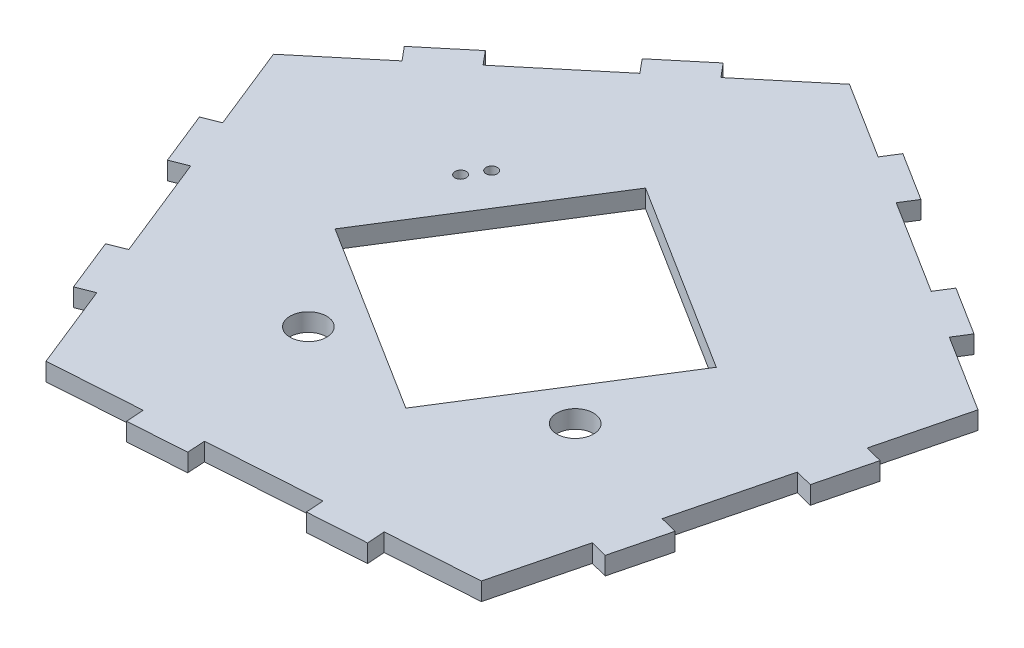
SolidWorks part; units mm, degrees
ref_plane "Front Plane" through (0, 0, 0) normal (0, 0, 1) x (1, 0, 0)
ref_plane "Top Plane" through (0, 0, 0) normal (0, 1, 0) x (1, 0, 0)
ref_plane "Right Plane" through (0, 0, 0) normal (1, 0, 0) x (0, 0, -1)
sketch "Sketch1" plane through (0, 0, 0) normal (0, 1, 0) x (1, 0, 0)
  line L1 (-59.9258, 15.1181) -> (-32.8962, -52.3211)
  line L2 (-32.8962, -52.3211) -> (39.5948, -47.4543)
  line L3 (39.5948, -47.4543) -> (57.3672, 22.9927)
  line L4 (57.3672, 22.9927) -> (-4.14, 61.6646)
  line L5 (-4.14, 61.6646) -> (-59.9258, 15.1181)
  circle A0 centre (0, 0) radius 50 construction
  dimension "D1" = 100
extrude "Boss-Extrude1" add sketch "Sketch1" along normal blind 3.18
ref_axis "Axis" through (0, 3.339, 0) along (0, -1, 0)
sketch "Axis Check" plane through (0, 3.18, 0) normal (0, 1, 0) x (1, 0, 0)
  line L0 (3.3493, -49.8877) -> (-4.14, 61.6646) construction
  line L1 (-32.8962, -52.3211) -> (39.5948, -47.4543) construction
  line L2 (57.3672, 22.9927) -> (-46.411, -18.6015) construction
  line L3 (-59.9258, 15.1181) -> (-32.8962, -52.3211) construction
  line L4 (-32.0329, 38.3913) -> (39.5948, -47.4543) construction
  line L5 (-4.14, 61.6646) -> (-59.9258, 15.1181) construction
  line L6 (-59.9258, 15.1181) -> (48.481, -12.2308) construction
  line L7 (39.5948, -47.4543) -> (57.3672, 22.9927) construction
  line L8 (-32.8962, -52.3211) -> (26.6136, 42.3287) construction
  line L9 (57.3672, 22.9927) -> (-4.14, 61.6646) construction
sketch "Sketch2" plane through (0, 0, 0) normal (0, -1, 0) x (1, 0, 0)
  line L0 (-53.8107, 0.1392) -> (-50.859, -1.0438)
  line L1 (-53.8107, 0.1392) -> (-50.1723, 9.2172)
  line L2 (-50.859, -1.0438) -> (-47.2205, 8.0342)
  line L3 (-50.1723, 9.2172) -> (-47.2205, 8.0342)
  line L4 (-59.9258, -15.1181) -> (-32.8962, 52.3211) construction
  line L5 (-42.6498, 27.9858) -> (-39.0113, 37.0638)
  line L6 (-42.6498, 27.9858) -> (-39.6981, 26.8028)
  line L7 (-39.0113, 37.0638) -> (-36.0596, 35.8808)
  line L8 (-39.6981, 26.8028) -> (-36.0596, 35.8808)
  line L9 (-46.411, 18.6015) -> (-19.2439, 7.7129) construction
  line L10 (-40.8306, 32.5248) -> (-37.8788, 31.3418) construction
  dimension "D1" = 3.18
  dimension "D2" = 9.78
  dimension "D3" = 10.11
extrude "Cut F" [suppressed] cut sketch "Sketch2" against normal through all
sketch "Sketch4" plane through (0, 3.18, 0) normal (0, 1, 0) x (1, 0, 0)
  line L9 (26.6136, 42.3287) -> (-26.6136, -42.3287) construction
  line L10 (57.3672, 22.9927) -> (-4.14, 61.6646) construction
  line L11 (-27.5769, -6.286) -> (-6.286, 27.5769)
  line L12 (-27.5769, -6.286) -> (6.286, -27.5769)
  line L13 (-6.286, 27.5769) -> (27.5769, 6.286)
  line L14 (6.286, -27.5769) -> (27.5769, 6.286)
  line L15 (-27.5769, -6.286) -> (27.5769, 6.286) construction
  line L16 (-6.286, 27.5769) -> (6.286, -27.5769) construction
  line L20 (0, 0) -> (39.0006, -24.5211) construction
  circle A0 centre (-14.9036, -23.7041) radius 3.25
  circle A1 centre (23.7041, -14.9036) radius 3.25
  point P5 (0, 0)
  point P6 (-14.9036, -23.7041)
  dimension "D3" = 6.5
  dimension "D1" = 40
  dimension "D2" = 40
  dimension "D4" = 8
  dimension "D5" = 8
extrude "Top Cut" cut sketch "Sketch4" against normal blind 10
sketch "Sketch7" plane through (0, 3.18, 0) normal (0, 1, 0) x (1, 0, 0)
  line L0 (0, 0) -> (26.6136, 42.3287) construction
  line L1 (57.3672, 22.9927) -> (-4.14, 61.6646) construction
  line L2 (1.0645, 1.6931) -> (-22.6395, 16.5968) construction
  line L3 (-6.1086, 1.4782) -> (-24.7686, 13.2105) construction
  line L5 (-6.286, 27.5769) -> (-27.5769, -6.286) construction
  circle A0 centre (-22.6395, 16.5968) radius 1
  circle A1 centre (-24.7686, 13.2105) radius 1
  dimension "D5" = 2
  dimension "D1" = 4
  dimension "D2" = 2
  dimension "D3" = 8
  dimension "D4" = 8
extrude "Top Cut 2" cut sketch "Sketch7" against normal through all
sketch "Sketch8" [suppressed] plane through (0, 3.18, 0) normal (0, 1, 0) x (1, 0, 0)
  line L0 (3.3493, -49.8877) -> (-4.14, 61.6646) construction
  line L5 (-32.8962, -52.3211) -> (39.5948, -47.4543) construction
  line L6 (-17.9455, -31.2723) -> (21.9647, -28.5929)
  line L11 (-17.9455, -31.2723) -> (-21.9647, 28.5929)
  line L12 (21.9647, -28.5929) -> (17.9455, 31.2723)
  line L13 (-21.9647, 28.5929) -> (17.9455, 31.2723)
  point P4 (1.4955, -22.2759)
  dimension "D1" = 60
  dimension "D2" = 40
  dimension "D3" = 20
extrude "Bottom Cut" [suppressed] cut sketch "Sketch8" against normal blind 10
sketch "Sketch9" [suppressed] plane through (0, 3.18, 0) normal (0, 1, 0) x (1, 0, 0)
  line L0 (19.9551, 1.3397) -> (-19.9551, -1.3397) construction
  line L1 (21.9647, -28.5929) -> (17.9455, 31.2723) construction
  line L2 (-21.9647, 28.5929) -> (-17.9455, -31.2723) construction
  line L3 (-19.9551, -1.3397) -> (-44.4689, -2.9855) construction
  line L4 (19.9551, 1.3397) -> (42.6839, 2.8657) construction
  line L5 (-32.8962, -52.3211) -> (39.5948, -47.4543) construction
  line L6 (-29.6051, -6.8886) -> (-32.3788, -7.0748)
  line L7 (-29.6051, -6.8886) -> (-30.2602, 2.8694)
  line L8 (-30.2602, 2.8694) -> (-33.0339, 2.6832)
  line L9 (-32.3788, -7.0748) -> (-33.0339, 2.6832)
  line L10 (-29.6051, -6.8886) -> (-33.0339, 2.6832) construction
  line L11 (-30.2602, 2.8694) -> (-32.3788, -7.0748) construction
  line L12 (33.0339, -2.6832) -> (30.2602, -2.8694)
  line L13 (33.0339, -2.6832) -> (32.3788, 7.0748)
  line L14 (32.3788, 7.0748) -> (29.6051, 6.8886)
  line L15 (30.2602, -2.8694) -> (29.6051, 6.8886)
  line L16 (33.0339, -2.6832) -> (29.6051, 6.8886) construction
  line L17 (32.3788, 7.0748) -> (30.2602, -2.8694) construction
  line L18 (-32.8962, -52.3211) -> (39.5948, -47.4543) construction
  point P6 (-31.3195, -2.1027)
  point P13 (31.3195, 2.1027)
  dimension "D1" = 9.78
  dimension "D4" = 9.78
  dimension "D5" = 10
  dimension "D6" = 10
  dimension "D3" = 2.78
  dimension "D2" = 2.78
extrude "Battery Holder Cut" [suppressed] cut sketch "Sketch9" against normal blind 3.18
sketch "Sketch3" plane through (0, 3.18, 0) normal (0, 1, 0) x (1, 0, 0)
  line L0 (0, 0) -> (-40.9819, 49.1167) construction
  line L1 (-49.5112, 27.9494) -> (-45.4366, 23.066)
  line L3 (-45.4366, 23.066) -> (-37.5894, 29.6135)
  line L4 (-41.664, 34.4969) -> (-37.5894, 29.6135)
  line L5 (-4.14, 61.6646) -> (-59.9258, 15.1181) construction
  line L6 (-71.9961, 5.0469) -> (-69.9588, 2.6052)
  line L7 (-71.9961, 5.0469) -> (-47.4739, 25.5077)
  line L14 (-26.4764, 47.1691) -> (-22.4018, 42.2857)
  line L16 (-22.4018, 42.2857) -> (-14.5546, 48.8333)
  line L17 (-18.6292, 53.7166) -> (-14.5546, 48.8333)
  line L18 (-42.539, 27.5695) -> (-41.513, 26.3398) construction
  line L19 (-49.5112, 27.9494) -> (-41.664, 34.4969)
  line L21 (-26.4764, 47.1691) -> (-18.6292, 53.7166)
  line L22 (-16.5919, 51.275) -> (4.7866, 69.1127)
  line L23 (-39.6267, 32.0552) -> (-24.4391, 44.7274)
  line M18 (-4.14, 61.6646) -> (-59.9258, 15.1181)
  dimension "D1" = 3.18
  dimension "D2" = 10.22
  dimension "D3" = 9.89
  dimension "D4" = 100
extrude "Extrude M" add sketch "Sketch3" against normal up to surface (3.18 mm away) contours L21 L14 L7 L17 | L19 L1 L4 M18 region at (-44.5689, 3.18, -30.0023) region at (-21.5341, 3.18, -49.222) up to face at (-22.6395, 0, -15.5968)
pattern_circular "Circle F" [suppressed] count 5 over 360 about axis through (0, 3.339, 0) along (0, -1, 0) of bodies 173
pattern_circular "Circle M" count 5 over 360 about axis through (0, 3.339, 0) along (0, -1, 0) of "Extrude M"
pattern_circular "Circle Side F" [suppressed] count 5 over 360 about axis through (0, 3.339, 0) along (0, -1, 0) of bodies 173
pattern_circular "Circle Side M" [suppressed] count 5 over 360 about axis through (0, 3.339, 0) along (0, -1, 0) of bodies 168
equation "\"kerf\"= .22mm"
equation "\"tabWidthF\"= 10 - \"kerf\""
equation "\"tabThickness\"= 3.18"
equation "\"D1@Sketch2\"=\"tabThickness\""
equation "\"tabWidthM\"= 10 + \"kerf\""
equation "\"halfkerf\"= \"kerf\" / 2.00mm"
equation "\"D1@Sketch9\"=\"tabWidthF\""
equation "\"D4@Sketch9\"=\"tabWidthF\""
equation "\"D1@Battery Holder Cut\" = \"tabThickness\""
equation "\"tabLength\" = \"kerf\" + 12"
